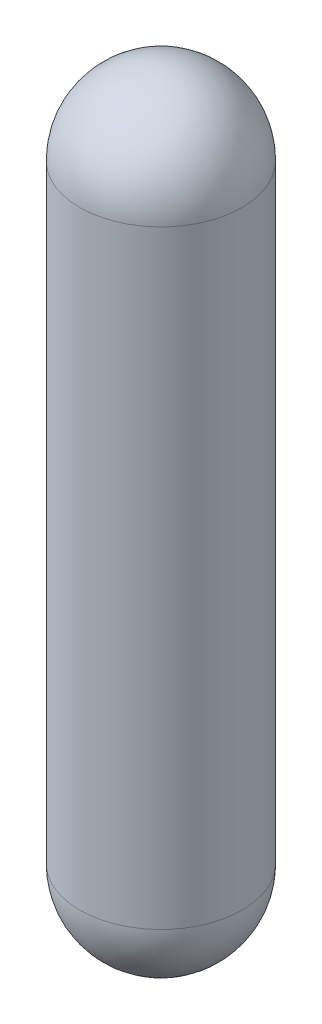
SolidWorks part; units mm, degrees
ref_plane "Front Plane" through (0, 0, 0) normal (0, 0, 1) x (1, 0, 0)
ref_plane "Top Plane" through (0, 0, 0) normal (0, 1, 0) x (1, 0, 0)
ref_plane "Right Plane" through (0, 0, 0) normal (1, 0, 0) x (0, 0, -1)
sketch "Sketch1" plane through (0, 0, 0) normal (0, 1, 0) x (1, 0, 0)
  circle A0 centre (0, 0) radius 10
  dimension "D1" = 20
extrude "Boss-Extrude1" add sketch "Sketch1" along normal blind 75
dome "Dome2" faces to dome 1 distance 10 reverse direction no elliptical dome no face at (0, 75, 10) parameters "D1"=10
dome "Dome3" faces to dome 1 distance 10 reverse direction no elliptical dome no face at (0, 0, 10) parameters "D1"=10
